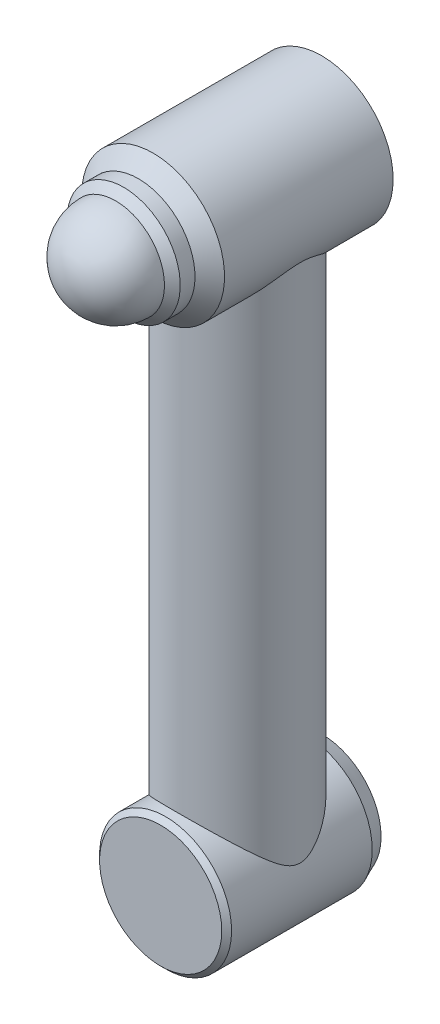
SolidWorks part; units mm, degrees
material "2014-T4"
ref_plane "Front Plane" through (0, 0, 0) normal (0, 0, 1) x (1, 0, 0)
ref_plane "Top Plane" through (0, 0, 0) normal (0, 1, 0) x (1, 0, 0)
ref_plane "Right Plane" through (0, 0, 0) normal (1, 0, 0) x (0, 0, -1)
sketch "Sketch1" plane through (0, 0, 0) normal (0, 0, 1) x (1, 0, 0)
  circle A0 centre (0, 0) radius 72.5
  dimension "D1" = 145
extrude "Boss-Extrude1" add sketch "Sketch1" along normal blind 294
fillet "Fillet1" radius 72.5 1 edges at (72.5, 0, 294)
sketch "Sketch2" plane through (0, 0, 0) normal (0, 1, 0) x (1, 0, 0)
  circle A0 centre (0, -85.5) radius 63.5
  dimension "D2" = 127
  dimension "D1" = 85.5
extrude "Boss-Extrude2" add sketch "Sketch2" against normal blind 584.2
ref_axis "Axis1" through (0, -578.1056, 85.5) along (0, 1, 0)
ref_plane "Plane1" through (0, 0, 85.5) normal (0, 0, 1) x (1, 0, 0)
sketch "Sketch3" plane through (0, 0, 85.5) normal (0, 0, 1) x (1, 0, 0)
  line L0 (-63.5, -584.2) -> (63.5, -584.2) construction
  line L1 (-63.5, -584.2) -> (63.5, -584.2)
  circle A0 centre (0, -584.2) radius 67
  dimension "D1" = 134
extrude "Boss-Extrude3" add sketch "Sketch3" along normal blind 78 and the other way blind 85.75 contours A0
chamfer "Chamfer1" distance 5 angle 45 1 edges at (67, -584.2, 163.5)
chamfer "Chamfer2" distance 7 distance2 16 1 edges at (67, -584.2, -0.25) first distance on face at (67, -584.2, -0.25)
sketch "Sketch4" plane through (0, 0, 0) normal (0, 1, 0) x (1, 0, 0)
  line L0 (0, -151.1483) -> (81.1092, -151.1483)
  line L1 (72.5, -151.1483) -> (72.5, -171.1483)
  line L2 (72.5, -171.1483) -> (57.5, -186.1483)
  line L3 (57.5, -186.1483) -> (57.5, -201.1483)
  line L4 (57.5, -201.1483) -> (49.5, -209.1483)
  line L5 (0, -258.6483) -> (0, -319.8813)
  line L6 (0, -319.8813) -> (156.3048, -319.8813)
  line L7 (156.3048, -319.8813) -> (156.3048, -151.1483)
  line L8 (156.3048, -151.1483) -> (72.5, -151.1483)
  arc A0 (49.5, -209.1483) -> (0, -258.6483) centre (0, -209.1483) cw
  dimension "D1" = 49.5
  dimension "D2" = 72.5
  dimension "D3" = 20
  dimension "D4" = 15
  dimension "D5" = 15
  dimension "D6" = 49.5
  dimension "D7" = 15
  dimension "D8" = 8
revolve "Cut-Revolve1" cut sketch "Sketch4" angle 360 about L5 region at (91.6418, 0, 246.271)
shell "Shell1" thickness 10 removed face at (60, -584.2, -0.25) removed face at (72.5, 0, 0)
